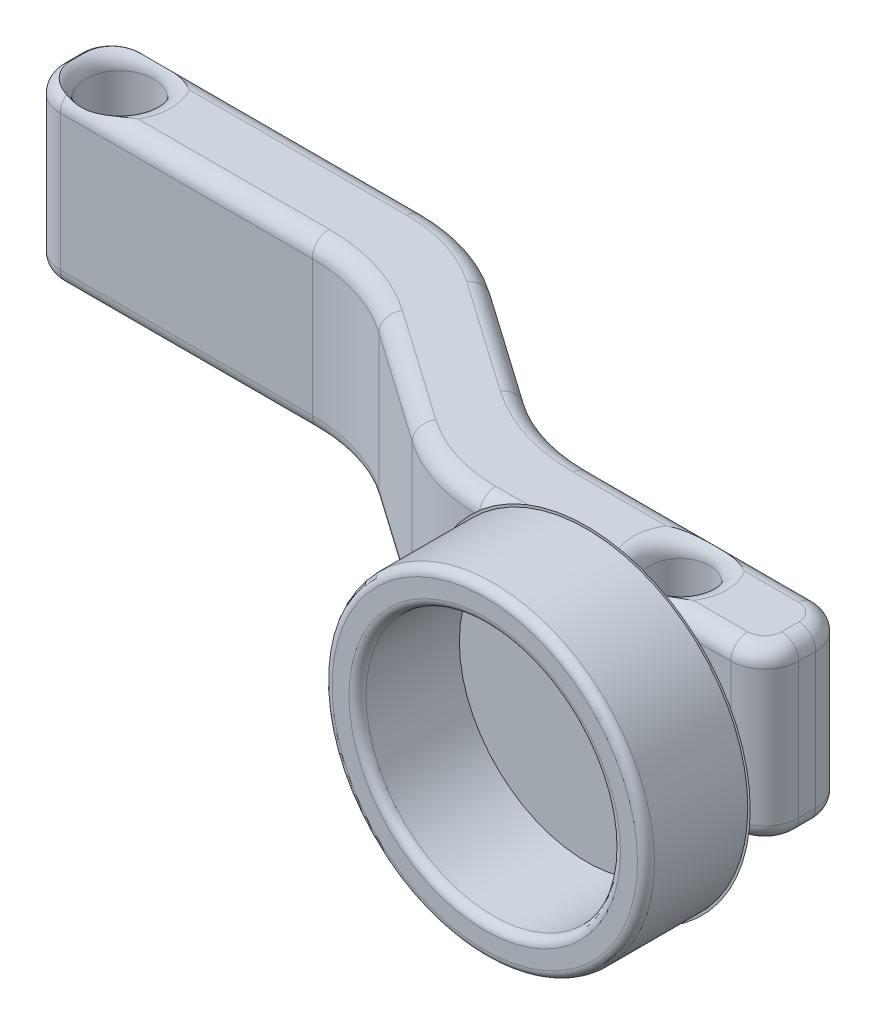
SolidWorks part; units mm, degrees
ref_plane "Front Plane" through (0, 0, 0) normal (0, 0, 1) x (1, 0, 0)
ref_plane "Top Plane" through (0, 0, 0) normal (0, 1, 0) x (1, 0, 0)
ref_plane "Right Plane" through (0, 0, 0) normal (1, 0, 0) x (0, 0, -1)
sketch "Sketch1" plane through (0, 0, 0) normal (0, 1, 0) x (1, 0, 0)
  line L0 (-2, 0) -> (-16.847, 0)
  line L1 (-22.5828, 1.8085) -> (-29.1374, 6.398)
  line L2 (-34.8731, 8.2065) -> (-49.7201, 8.2065)
  line L3 (-51.7201, 10.2065) -> (-51.7201, 11.2065)
  line L4 (-49.7201, 13.2065) -> (-33.2966, 13.2065)
  line L5 (-27.5609, 11.398) -> (-21.0063, 6.8085)
  line L6 (-15.2705, 5) -> (-2, 5)
  line L7 (0, 3) -> (0, 2)
  arc A0 (-16.847, 0) -> (-22.5828, 1.8085) centre (-16.847, 10) cw
  arc A1 (-21.0063, 6.8085) -> (-15.2705, 5) centre (-15.2705, 15) ccw
  arc A2 (-29.1374, 6.398) -> (-34.8731, 8.2065) centre (-34.8731, -1.7935) ccw
  arc A3 (-33.2966, 13.2065) -> (-27.5609, 11.398) centre (-33.2966, 3.2065) cw
  arc A4 (-2, 0) -> (0, 2) centre (-2, 2) ccw
  arc A5 (-2, 5) -> (0, 3) centre (-2, 3) cw
  arc A6 (-49.7201, 8.2065) -> (-51.7201, 10.2065) centre (-49.7201, 10.2065) cw
  arc A7 (-51.7201, 11.2065) -> (-49.7201, 13.2065) centre (-49.7201, 11.2065) cw
  point P11 (-20, 0)
  point P16 (-31.7201, 8.2065)
  point P21 (0, 0)
  point P26 (-51.7201, 8.2065)
  point P29 (-51.7201, 13.2065)
  dimension "D7" = 10
  dimension "D8" = 2
  dimension "D1" = 5
  dimension "D2" = 5
  dimension "D3" = 5
  dimension "D4" = 35
  dimension "D5" = 20
  dimension "D6" = 20
extrude "Boss-Extrude1" add sketch "Sketch1" along normal blind 10
sketch "Sketch2" plane through (0, 10, 0) normal (0, 1, 0) x (1, 0, 0)
  line L0 (-51.7201, 11.2065) -> (-51.7201, 10.2065) construction
  line L1 (-51.7201, 10.7065) -> (-48.7201, 10.7065) construction
  line L2 (0, 2.5) -> (-7.5, 2.5) construction
  line L3 (0, 2) -> (0, 3) construction
  circle A0 centre (-7.5, 2.5) radius 1.75
  circle A1 centre (-48.7201, 10.7065) radius 2
  dimension "D1" = 3.5
  dimension "D2" = 3
  dimension "D3" = 7.5
extrude "Cut-Extrude1" cut sketch "Sketch2" against normal blind 10
fillet "Fillet2" radius 1 36 edges at (-9.4235, 0, 0) (-0.5858, 0, -0.5858) (0, 0, -2.5) (-0.5858, 0, -4.4142) (-8.6353, 0, -5) (-18.2776, 0, -5.4628) (-24.2836, 0, -9.1033) (-30.2896, 0, -12.7437) (-41.5084, 0, -13.2065) (-51.1343, 0, -12.6207) (-51.7201, 0, -10.7065) (-51.1343, 0, -8.7923) (-42.2966, 0, -8.2065) (-31.8661, 0, -7.7437) (-25.8601, 0, -4.1033) (-19.8541, 0, -0.4628) (-7.5, 0, -0.75) (-25.8601, 10, -4.1033) (-31.8661, 10, -7.7437) (-42.2966, 10, -8.2065) (-51.1343, 10, -8.7923) (-51.7201, 10, -10.7065) (-51.1343, 10, -12.6207) (-41.5084, 10, -13.2065) (-30.2896, 10, -12.7437) (-24.2836, 10, -9.1033) (-18.2776, 10, -5.4628) (-8.6353, 10, -5) (-0.5858, 10, -4.4142) (0, 10, -2.5) (-0.5858, 10, -0.5858) (-9.4235, 10, 0) (-19.8541, 10, -0.4628) (-7.5, 10, -0.75) (-48.7201, 0, -8.7065) (-48.7201, 10, -8.7065)
sketch "Sketch4" plane through (0, 0, 0) normal (0, 0, 1) x (1, 0, 0)
  line L0 (0, 5) -> (-7.5, 5) construction
  line L1 (0, 9) -> (0, 1) construction
  circle A0 centre (-7.5, 5) radius 4
  dimension "D1" = 7.5
  dimension "D2" = 8
extrude "Boss-Extrude3" add sketch "Sketch4" along normal blind 3 draft 62 draft outward yes
sketch "Sketch3" plane through (0, 0, 3) normal (0, 0, 1) x (1, 0, 0)
  line L0 (-7.5, 5) -> (0, 5) construction
  line L2 (0, 9) -> (0, 1) construction
  circle A0 centre (-7.5, 5) radius 7.5
  circle A1 centre (-7.5, 5) radius 9.5
  dimension "D2" = 15
  dimension "D3" = 19
  dimension "D1" = 7.5
extrude "Boss-Extrude2" add sketch "Sketch3" along normal blind 6 separate body
fillet "Fillet4" radius 0.5 2 edges at (0, 5, 9) (2, 5, 9)
